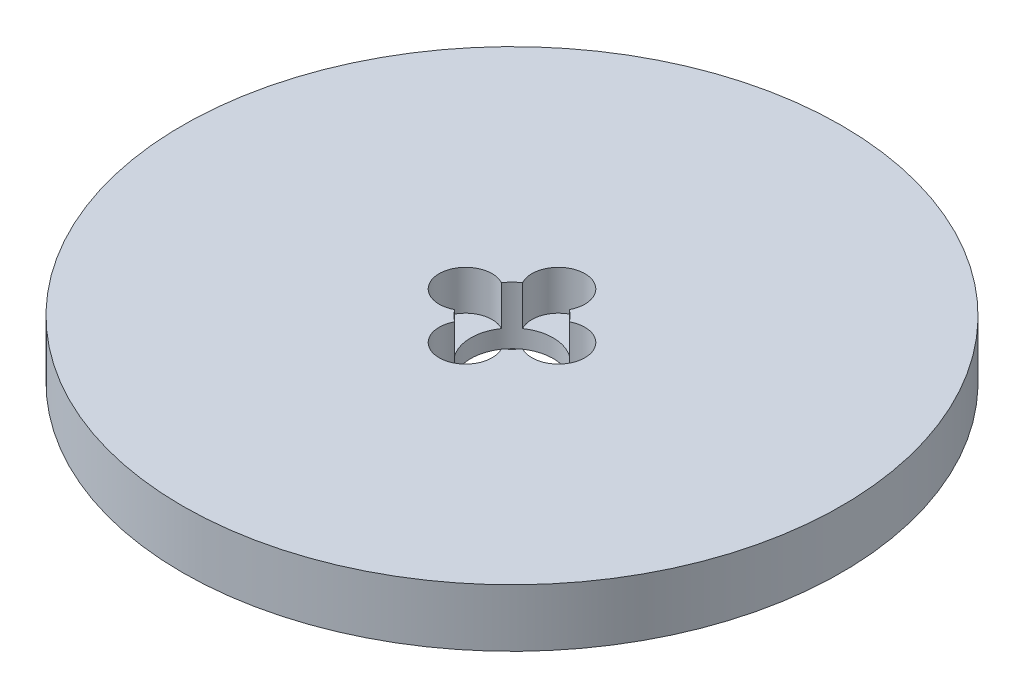
SolidWorks part; units mm, degrees
ref_plane "Front Plane" through (0, 0, 0) normal (0, 0, 1) x (1, 0, 0)
ref_plane "Top Plane" through (0, 0, 0) normal (0, 1, 0) x (1, 0, 0)
ref_plane "Right Plane" through (0, 0, 0) normal (1, 0, 0) x (0, 0, -1)
sketch "Sketch1" plane through (0, 0, 0) normal (0, 1, 0) x (1, 0, 0)
  circle A0 centre (0, 0) radius 80
  dimension "FLANGE_OD" = 160
extrude "Boss-Extrude1" add sketch "Sketch1" along normal blind 14
sketch "Sketch2" plane through (0, 0, 0) normal (0, 1, 0) x (1, 0, 0)
  circle A0 centre (0, 0) radius 10
  dimension "BORE_D" = 20
extrude "Cut-Extrude1" cut sketch "Sketch2" along normal through all
sketch "Sketch3" plane through (0, 14, 0) normal (0, 1, 0) x (1, 0, 0)
  circle A0 centre (0, 0) radius 11.2622 construction
  circle A1 centre (-11.2622, 0) radius 6.4302
  dimension "BOLT_D" = 12.8603
  dimension "BOLT_PCD" = 22.5244
extrude "Cut-Extrude2" cut sketch "Sketch3" against normal blind 9.647
pattern_circular "CirPattern1" count 4 over 360 about axis through (0, 0, 0) along (0, 1, 0) of "Cut-Extrude2"
